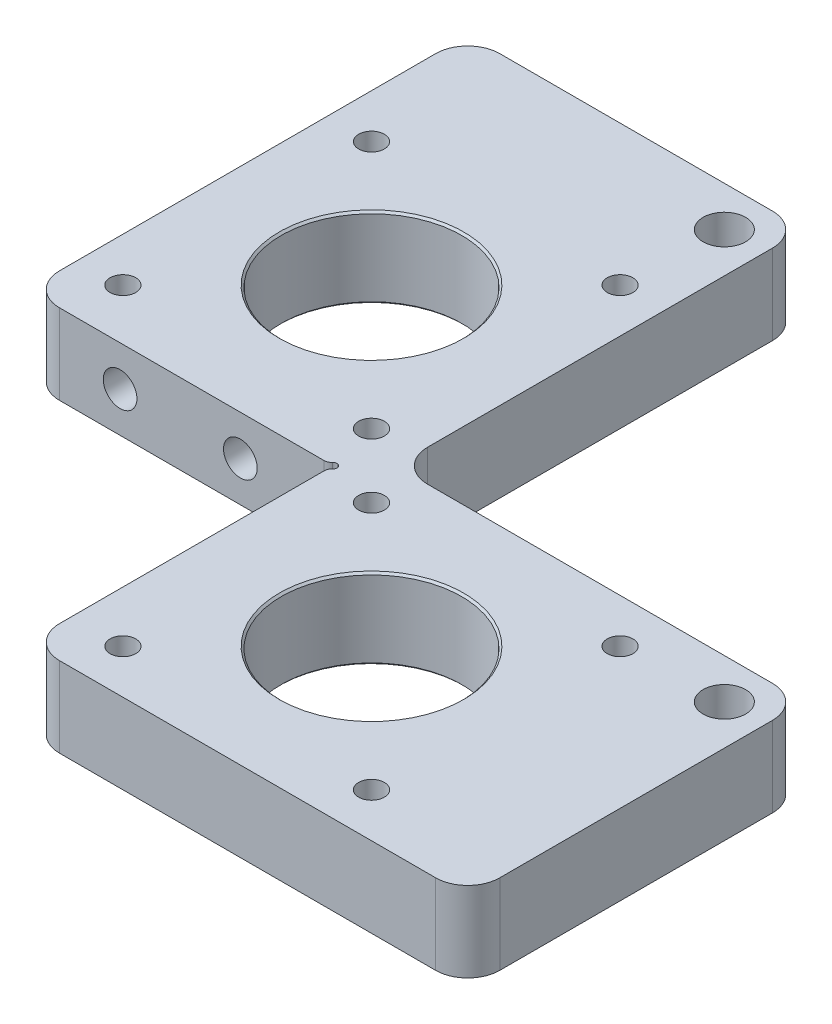
SolidWorks part; units mm, degrees
material "AISI 1045 Steel, cold drawn"
ref_plane "Front Plane" through (0, 0, 0) normal (0, 0, 1) x (1, 0, 0)
ref_plane "Top Plane" through (0, 0, 0) normal (0, 1, 0) x (1, 0, 0)
ref_plane "Right Plane" through (0, 0, 0) normal (1, 0, 0) x (0, 0, -1)
sketch "Sketch1" plane through (0, 0, 0) normal (0, 1, 0) x (1, 0, 0)
  line L1 (60, -21) -> (18, -21) construction
  line L2 (60, -21) -> (60, 21) construction
  line L3 (60, 21) -> (18, 21) construction
  line L4 (18, -21) -> (18, 21) construction
  line L5 (60, -21) -> (18, 21) construction
  line L6 (60, 21) -> (18, -21) construction
  line L7 (21, 18) -> (-21, 18) construction
  line L8 (21, 18) -> (21, 60) construction
  line L9 (21, 60) -> (-21, 60) construction
  line L10 (-21, 18) -> (-21, 60) construction
  line L11 (21, 18) -> (-21, 60) construction
  line L12 (21, 60) -> (-21, 18) construction
  line L14 (60, -21) -> (60, 21)
  line L15 (60, 21) -> (21, 21)
  line L16 (21, 21) -> (21, 60)
  line L17 (21, 60) -> (-21, 60)
  line L18 (-21, 60) -> (-21, 18)
  line L19 (-21, 18) -> (18, 18)
  line L20 (18, 18) -> (18, -21)
  line L21 (18, -21) -> (60, -21)
  point P0 (39, 0)
  point P5 (0, 39)
  point P10 (21, 21)
  point P15 (21, 21)
  point P17 (0, 0)
  dimension "D1" = 42
  dimension "D2" = 39
  dimension "D3" = 39
extrude "Boss-Extrude1" add sketch "Sketch1" along normal blind 10
hole_wizard "Ø22.5 (22.5) Diameter Hole1" positions "Sketch5" profile "Sketch7" hole size "Ø22.5" standard "ANSI Metric" end condition through all
sketch "Sketch5" plane through (0, 10, 0) normal (0, 1, 0) x (1, 0, 0)
  point P0 (0, 39)
  point P3 (39, 0)
sketch "Sketch7" plane through (0, 10, -39) normal (1, 0, 0) x (0, 0, 1)
  line L0 (0, 0) -> (0, 10)
  line L1 (0, 10) -> (11.25, 10)
  line L2 (11.25, 10) -> (11.25, 0)
  line L5 (11.25, 0) -> (0, 0)
  line L11 (0, -6.35) -> (0, 107.95) construction
  dimension "Thru Hole Dia." = 22.5
  dimension "Thru Hole Depth" = 10
sketch "Sketch8" plane through (0, 0, 0) normal (0, 1, 0) x (1, 0, 0)
  line L0 (21, 60) -> (-21, 18) construction
  line L1 (15.5, 23.5) -> (-15.5, 23.5)
  line L2 (15.5, 23.5) -> (15.5, 54.5)
  line L3 (15.5, 54.5) -> (-15.5, 54.5)
  line L4 (-15.5, 23.5) -> (-15.5, 54.5)
  line L5 (15.5, 23.5) -> (-15.5, 54.5) construction
  line L6 (15.5, 54.5) -> (-15.5, 23.5) construction
  line L7 (21, 18) -> (-21, 60) construction
  line L8 (60, 21) -> (18, -21) construction
  line L9 (23.5, -15.5) -> (54.5, -15.5)
  line L10 (23.5, -15.5) -> (23.5, 15.5)
  line L11 (23.5, 15.5) -> (54.5, 15.5)
  line L12 (54.5, -15.5) -> (54.5, 15.5)
  line L13 (23.5, -15.5) -> (54.5, 15.5) construction
  line L14 (23.5, 15.5) -> (54.5, -15.5) construction
  point P0 (0, 39)
  point P9 (39, 0)
  dimension "D1" = 31
hole_wizard "CBORE for M3 SHCS1" positions "Sketch9" profile "Sketch10" counterbore size "M3" standard "ANSI Metric" end condition through all
sketch "Sketch9" plane through (0, 0, 0) normal (0, -1, 0) x (-1, 0, 0)
  point P0 (-54.5, 15.5)
  point P3 (-23.5, 15.5)
  point P6 (-23.5, -15.5)
  point P9 (-54.5, -15.5)
  point P12 (-15.5, 54.5)
  point P15 (-15.5, 23.5)
  point P18 (15.5, 23.5)
  point P21 (15.5, 54.5)
sketch "Sketch10" plane through (54.5, 0, -15.5) normal (1, 0, 0) x (0, 0, -1)
  line L0 (0, 0) -> (0, 10)
  line L1 (0, 10) -> (1.6, 10)
  line L3 (1.6, 10) -> (1.6, 3)
  line L4 (1.6, 3) -> (3.25, 3)
  line L5 (3.25, 3) -> (3.25, 0)
  line L7 (3.25, 0) -> (0, 0)
  line L11 (0, -6.35) -> (0, 107.95) construction
  dimension "Thru Hole Dia." = 3.2
  dimension "Thru Hole Depth" = 10
  dimension "C'Bore Dia." = 6.5
  dimension "C'Bore Depth" = 3
sketch "Sketch16" plane through (0, 10, 0) normal (0, 1, 0) x (1, 0, 0)
  line L1 (17.1, 17.1) -> (-21, 17.1)
  line L2 (17.1, 17.1) -> (17.1, -21)
  line L6 (-21, 17.1) -> (-21, 18)
  line L7 (-21, 18) -> (18, 18)
  line L8 (18, 18) -> (18, -21)
  line L9 (18, -21) -> (17.1, -21)
  circle A0 centre (39, 0) radius 11.25 construction
  dimension "D1" = 21.9
extrude "Boss-Extrude2" add sketch "Sketch16" against normal up to surface (10 mm away) up to face at (54.5, 0, -18.75)
hole_wizard "Tap Drill for M5x0.8 Tap1" positions "Sketch13" profile "Sketch15" hole size "M5x0.8" standard "ANSI Metric"
sketch "Sketch13" plane through (0, 0, -17.1) normal (0, 0, 1) x (1, 0, 0)
  line L4 (-21, 0) -> (-21, 10) construction
  line L5 (-1.95, 10) -> (-1.95, 0) construction
  line L6 (-21, 10) -> (17.1, 10) construction
  line L7 (17.1, 0) -> (-21, 0) construction
  line L9 (-9.45, 5) -> (5.55, 5) construction
  point P0 (5.55, 5)
  point P2 (-9.45, 5)
  point P25 (-21, 5)
  point P39 (-1.95, 5)
  point P40 (-1.95, 5)
  dimension "D1" = 15
sketch "Sketch15" plane through (5.55, 5, -17.1) normal (1, 0, 0) x (0, -1, 0)
  line L0 (0, 0) -> (0, 9.2618)
  line L1 (0, 9.2618) -> (2.1, 8)
  line L2 (2.1, 8) -> (2.1, 0)
  line L5 (2.1, 0) -> (0, 0)
  line L10 (0, 9.2618) -> (-2.1, 8) construction
  line L11 (0, -6.35) -> (0, 107.95) construction
  dimension "Hole Dia." = 4.2
  dimension "Hole Depth" = 8
  dimension "Drill Angle" = 118
ref_plane "Plane1" through (0, 0, 0) normal (0.7071, 0, 0.7071) x (0.7071, 0, -0.7071)
sketch "Sketch17" plane through (0, 10, 0) normal (0, 1, 0) x (1, 0, 0)
  line L0 (17.1, -21) -> (60, -21) construction
  line L1 (60, 21) -> (72, 21)
  line L2 (60, 21) -> (60, -21)
  line L3 (60, -21) -> (72, -21)
  line L4 (72, 21) -> (72, -21)
  line L5 (60, -21) -> (60, 21) construction
  point P5 (60, -21)
  dimension "D1" = 12
extrude "Boss-Extrude3" add sketch "Sketch17" against normal up to surface (10 mm away) up to face at (54.5, 0, -18.75)
hole_wizard "M5 Clearance Hole1" positions "Sketch18" profile "Sketch19" hole size "M5" standard "ANSI Metric" end condition through all
sketch "Sketch18" plane through (0, 10, 0) normal (0, 1, 0) x (1, 0, 0)
  line L0 (72, 21) -> (21, 21) construction
  line L1 (72, -21) -> (72, 21) construction
  point P0 (67, 16)
  dimension "D1" = 5
  dimension "D2" = 5
sketch "Sketch19" plane through (67, 10, -16) normal (1, 0, 0) x (0, 0, 1)
  line L0 (0, 0) -> (0, 10)
  line L1 (0, 10) -> (2.65, 10)
  line L2 (2.65, 10) -> (2.65, 0)
  line L5 (2.65, 0) -> (0, 0)
  line L11 (0, -6.35) -> (0, 107.95) construction
  dimension "Thru Hole Dia." = 5.3
  dimension "Thru Hole Depth" = 10
mirror "Mirror1" about plane through (0, 0, 0) normal (0.7071, 0, 0.7071) of "Tap Drill for M5x0.8 Tap1", "Boss-Extrude3", "M5 Clearance Hole1"
fillet "Fillet6" radius 4 7 edges at (72, 5, 21) (72, 5, -21) (21, 5, -21) (21, 5, -72) (-21, 5, -72) (17.1, 5, 21) (-21, 5, -17.1)
sketch "Sketch20" plane through (0, 0, 0) normal (0, -1, 0) x (1, 0, 0)
  circle A0 centre (17.1, -17.1) radius 0.5
  dimension "D1" = 1
extrude "Cut-Extrude1" cut sketch "Sketch20" against normal through all
fillet "Fillet5" radius 1 2 edges at (17.1, 5, -16.6) (16.6, 5, -17.1)
chamfer "Chamfer1" distance 0.25 angle 45 4 edges at (39, 10, 11.25) (39, 0, 11.25) (0, 10, -27.75) (0, 0, -27.75)
